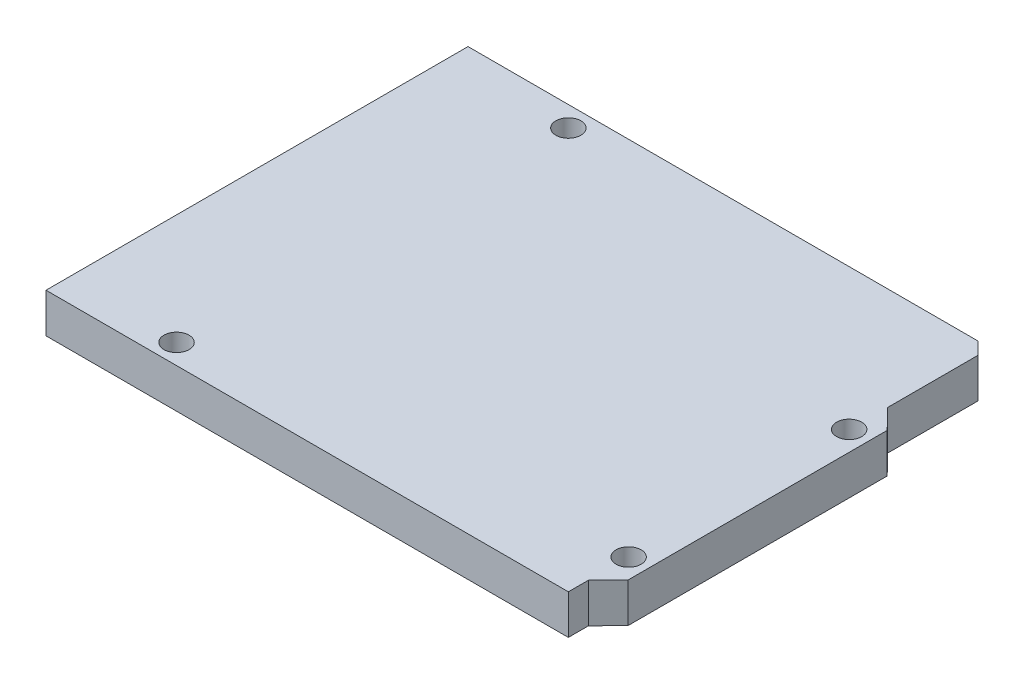
SolidWorks part; units mm, degrees
ref_plane "Front Plane" through (0, 0, 0) normal (0, 0, 1) x (1, 0, 0)
ref_plane "Top Plane" through (0, 0, 0) normal (0, 1, 0) x (1, 0, 0)
ref_plane "Right Plane" through (0, 0, 0) normal (1, 0, 0) x (0, 0, -1)
sketch "Sketch2" plane through (0, 0, 0) normal (0, 1, 0) x (1, 0, 0)
  line L0 (-53.4803, 37.7956) -> (11.0249, 37.7956)
  line L1 (11.0249, 37.7956) -> (12.5897, 36.2308)
  line L2 (12.5897, 36.2308) -> (12.5897, 24.8031)
  line L3 (12.5897, 24.8031) -> (15.0697, 22.2631)
  line L4 (15.0697, 22.2631) -> (15.0697, -10.5029)
  line L5 (15.0697, -10.5029) -> (12.5897, -13.0429)
  line L6 (12.5897, -13.0429) -> (12.5897, -15.5829)
  line L7 (12.5897, -15.5829) -> (-53.4803, -15.5829)
  line L8 (-53.4803, -15.5829) -> (-53.4803, 37.7956)
  circle A0 centre (-38.2103, 35.2171) radius 1.5875
  circle A1 centre (12.5579, 19.9653) radius 1.5875
  circle A2 centre (12.5897, -7.9629) radius 1.5875
  circle A3 centre (-39.5103, -13.0429) radius 1.5875
  dimension "D1" = 64.5052
  dimension "D2" = 2.2129
  dimension "D3" = 11.4277
  dimension "D4" = 3.5499
  dimension "D5" = 32.766
  dimension "D6" = 3.5499
  dimension "D7" = 2.54
  dimension "D8" = 66.07
  dimension "D9" = 53.3785
  dimension "D10" = 135
  dimension "D11" = 135.685
extrude "Boss-Extrude1" add sketch "Sketch2" along normal blind 5
